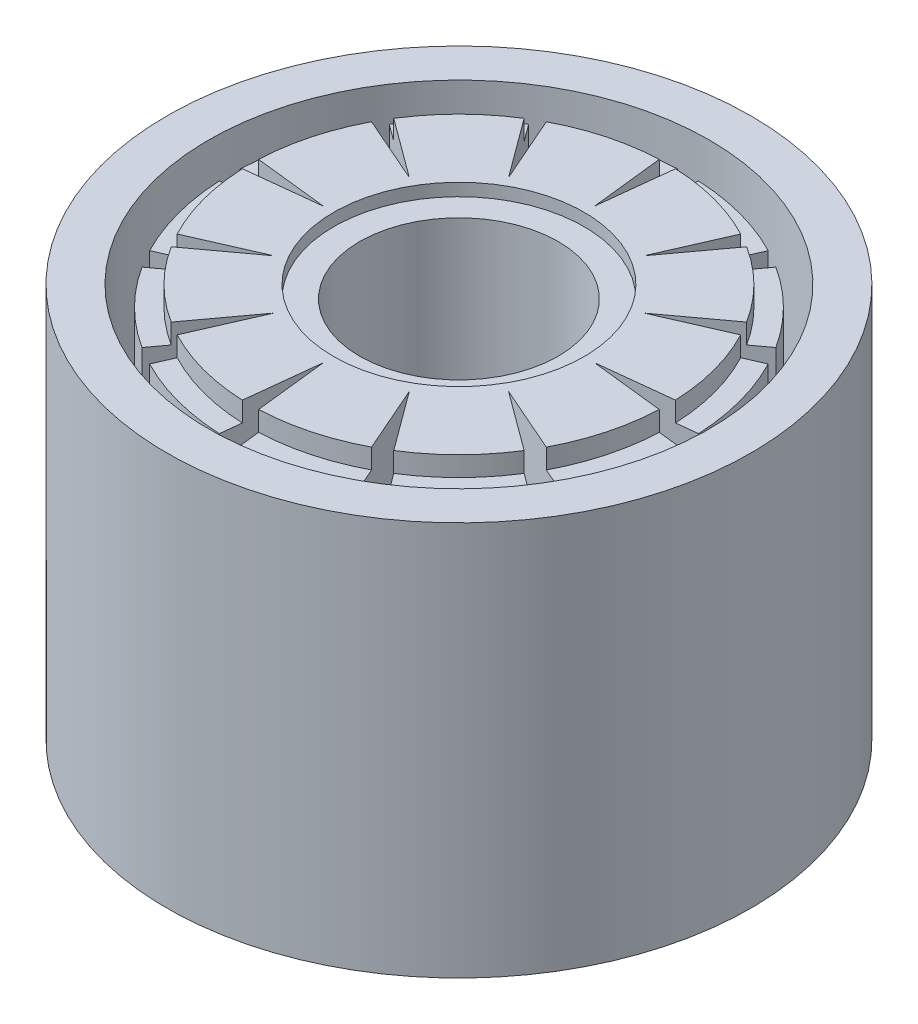
SolidWorks part; units mm, degrees
material "Cast Stainless Steel"
ref_plane "Front Plane" through (0, 0, 0) normal (0, 0, 1) x (1, 0, 0)
ref_plane "Top Plane" through (0, 0, 0) normal (0, 1, 0) x (1, 0, 0)
ref_plane "Right Plane" through (0, 0, 0) normal (1, 0, 0) x (0, 0, -1)
sketch "Sketch2" plane through (0, 0, 0) normal (0, 0, 1) x (1, 0, 0)
  line L0 (0, 0) -> (0, 21.3606) construction
  line L5 (4, 0) -> (12.5, 0)
  line L6 (12.5, 0) -> (14, 4)
  line L7 (14, 4) -> (14, 6)
  line L8 (14, 6) -> (6, 6)
  line L9 (6, 6) -> (6, 6.1)
  line L10 (6, 6.1) -> (11, 6.1)
  line L11 (11, 6.1) -> (11, 25)
  line L12 (11, 25) -> (4, 25)
  line L13 (4, 25) -> (4, 22)
  line L14 (4, 22) -> (3, 22)
  line L15 (3, 22) -> (3, 3)
  line L16 (3, 3) -> (4, 3)
  line L17 (4, 3) -> (4, 0)
  line L18 (14, 6) -> (14, 20.2979) construction
  line L19 (10, 25) -> (10, 24.05)
  line L20 (10, 24.05) -> (11, 24.05)
  line L21 (10, 6.1) -> (10, 7.05)
  line L22 (10, 7.05) -> (11, 7.05)
  dimension "D1" = 28
  dimension "D2" = 6
  dimension "D3" = 1.5
  dimension "D4" = 4
  dimension "D5" = 6
  dimension "D6" = 8
  dimension "D7" = 3
  dimension "D8" = 19
  dimension "D9" = 12
  dimension "D10" = 3
  dimension "D11" = 0.1
  dimension "D12" = 1
  dimension "D13" = 17
revolve "Revolve1" add sketch "Sketch2" angle 360 about L0 region at (7.4506, 11.822, 0)
sketch "Sketch3" plane through (0, 0, 0) normal (0, 0, 1) x (1, 0, 0)
  line L0 (-11, 6.1) -> (11, 6.1) construction
  line L1 (14, 6.1) -> (12, 6.1)
  line L2 (14, 6.1) -> (14, 25)
  line L3 (14, 25) -> (12, 25)
  line L4 (12, 6.1) -> (12, 25)
  line L5 (11, 25) -> (-11, 25) construction
  line L6 (14, 4) -> (14, 6) construction
  line L7 (0, 0) -> (0, 26.8317) construction
  dimension "D1" = 2
revolve "Revolve2" add sketch "Sketch3" angle 360 about L7
sketch "Sketch4" plane through (0, 0, 0) normal (0, -1, 0) x (1, 0, 0)
  line L0 (0, 9.5) -> (0, -9.5) construction
  line L1 (-8, 0) -> (8, 0) construction
  circle A0 centre (-8, 0) radius 1.25
  circle A1 centre (0, 9.5) radius 1.25
  circle A2 centre (8, 0) radius 1.25
  circle A3 centre (0, -9.5) radius 1.25
  dimension "D3" = 2.5
  dimension "D1" = 16
  dimension "D2" = 19
extrude "Cut-Extrude1" cut sketch "Sketch4" against normal up to next (6 mm away)
sketch "Sketch5" plane through (0, 25, 0) normal (0, 1, 0) x (1, 0, 0)
  line L2 (0, 6.5) -> (-0.5, 10.9886)
  line L3 (0, 6.5) -> (0.5, 10.9886)
  circle A0 centre (0, 0) radius 6 construction
  circle A1 centre (0, 0) radius 6 construction
  circle A3 centre (0, 0) radius 11 construction
  arc A6 (-0.5, 10.9886) -> (0.5, 10.9886) centre (0, 0) cw
  circle A7 centre (0, 0) radius 6.5 construction
  circle A9 centre (0, 0) radius 11 construction
  point P13 (0, 11)
  dimension "D1" = 1
  dimension "D2" = 0.5
extrude "Cut-Extrude2" cut sketch "Sketch5" against normal up to surface (18.9 mm away) up to face at (0, 6.1, -10)
pattern_circular "CirPattern1" count 12 over 360 about axis through (0, 25, 0) along (0, -1, 0) of "Cut-Extrude2"
sketch "Sketch6" plane through (0, 25, 0) normal (0, 1, 0) x (1, 0, 0)
  circle A0 centre (0, 0) radius 6
  circle A1 centre (0, 0) radius 4.5
  dimension "D1" = 12
  dimension "D2" = 9
extrude "Cut-Extrude3" cut sketch "Sketch6" against normal blind 0.6
sketch "Sketch7" plane through (0, 0, 0) normal (1, 0, 0) x (0, 0, -1)
  line L0 (0, 0) -> (0, 6.7)
  line L2 (-6, 6.1) -> (6, 6.1) construction
  line L3 (-6, 6.1) -> (6, 6.1) construction
  line L4 (0, 0) -> (14, 0)
  line L5 (14, 0) -> (14, 6.1)
  line L6 (14, 4) -> (14, 6) construction
  line L7 (0, 6.7) -> (6, 6.7)
  line L8 (6, 6.7) -> (6, 6.1)
  line L9 (6, 6.1) -> (14, 6.1)
  line L11 (6, 25) -> (-6, 25) construction
  line L12 (6, 24.4) -> (-6, 24.4) construction
  line L13 (6, 25) -> (-6, 25) construction
  line L14 (6, 24.4) -> (-6, 24.4) construction
  line L15 (0, 25) -> (0, 24.4) construction
  point P16 (6, 5.5)
  point P17 (6, 6.9117)
revolve "Cut-Revolve1" cut sketch "Sketch7" angle 360 about L0
sketch "Sketch8" plane through (0, 6.7, 0) normal (0, -1, 0) x (1, 0, 0)
  circle A0 centre (0, 0) radius 4.7625
  dimension "D1" = 9.525
extrude "Cut-Extrude4" cut sketch "Sketch8" against normal through all
equation "\"D1@Sketch8\"=.375in"
